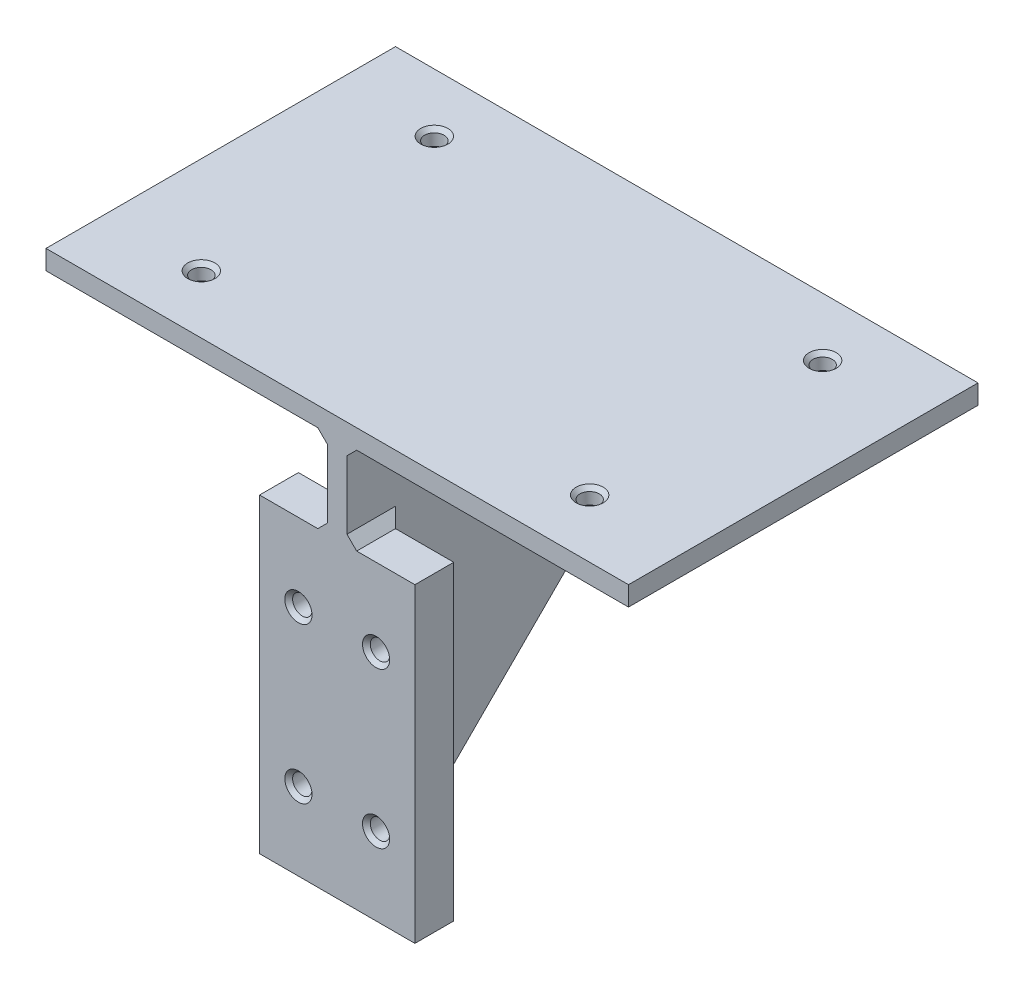
SolidWorks part; units mm, degrees
ref_plane "Front Plane" through (0, 0, 0) normal (0, 0, 1) x (1, 0, 0)
ref_plane "Top Plane" through (0, 0, 0) normal (0, 1, 0) x (1, 0, 0)
ref_plane "Right Plane" through (0, 0, 0) normal (1, 0, 0) x (0, 0, -1)
sketch "Sketch1" plane through (0, 0, 0) normal (0, 0, 1) x (1, 0, 0)
  line L1 (-20, -40) -> (20, -40)
  line L2 (-20, -40) -> (-20, 40)
  line L3 (-20, 40) -> (20, 40)
  line L4 (20, -40) -> (20, 40)
  line L5 (-20, -40) -> (20, 40) construction
  line L6 (-20, 40) -> (20, -40) construction
  point P0 (0, 0)
  dimension "D1" = 40
  dimension "D2" = 80
extrude "Boss-Extrude1" add sketch "Sketch1" along normal blind 10
sketch "Sketch2" plane through (0, 0, 10) normal (0, 0, 1) x (1, 0, 0)
  line L0 (0, 20) -> (0, -20) construction
  line L1 (-10, -20) -> (10, -20) construction
  line L2 (-10, -20) -> (-10, 20) construction
  line L3 (-10, 20) -> (10, 20) construction
  line L4 (10, -20) -> (10, 20) construction
  line L5 (-10, -20) -> (10, 20) construction
  line L6 (-10, 20) -> (10, -20) construction
  line L7 (-10, 0) -> (10, 0) construction
  circle A0 centre (-10, -20) radius 2.5
  circle A1 centre (10, -20) radius 2.5
  circle A2 centre (10, 20) radius 2.5
  circle A3 centre (-10, 20) radius 2.5
  point P0 (0, 0)
  dimension "D1" = 5
  dimension "D2" = 40
  dimension "D3" = 20
extrude "Cut-Extrude1" cut sketch "Sketch2" against normal blind 10
sketch "Sketch3" plane through (0, 0, 0) normal (1, 0, 0) x (0, 0, -1)
  line L0 (0, -40) -> (80, 40)
  line L3 (0, -40) -> (0, 40) construction
  line L4 (0, 40) -> (0, -40)
  line L5 (80, 40) -> (80, 65)
  line L8 (0, 40) -> (-10, 40)
  line L9 (-10, 40) -> (-10, 65)
  line L11 (-10, 65) -> (80, 65)
  dimension "D1" = 45
  dimension "D2" = 90
  dimension "D3" = 25
extrude "Boss-Extrude2" add sketch "Sketch3" along normal mid plane 5
sketch "Sketch4" plane through (0, 65, 0) normal (0, 1, 0) x (1, 0, 0)
  line L0 (2.5, 80) -> (-2.5, 80) construction
  line L1 (-75, -10) -> (75, -10)
  line L2 (-75, -10) -> (-75, 80)
  line L3 (-75, 80) -> (75, 80)
  line L4 (75, -10) -> (75, 80)
  line L5 (-75, -10) -> (75, 80) construction
  line L6 (-75, 80) -> (75, -10) construction
  line L7 (20, -10) -> (2.5, -10) construction
  line L8 (0, 0) -> (0, 80) construction
  point P0 (0, 35)
  point P12 (0, 0)
  dimension "D1" = 150
extrude "Boss-Extrude3" add sketch "Sketch4" along normal mid plane 5
chamfer "Chamfer1" distance 2.5 angle 45 6 edges at (-2.5, 40, 5) (-2.5, 0, 0) (2.5, 40, 5) (2.5, 0, 0) (2.5, 62.5, -35) (-2.5, 62.5, -35)
sketch "Sketch5" plane through (0, 67.5, 0) normal (0, 1, 0) x (1, 0, 0)
  line L0 (-75, -10) -> (75, 80) construction
  line L1 (0, 5) -> (0, 65) construction
  line L2 (-50, 5) -> (50, 5) construction
  line L3 (-50, 5) -> (-50, 65) construction
  line L4 (-50, 65) -> (50, 65) construction
  line L5 (50, 5) -> (50, 65) construction
  line L6 (-50, 5) -> (50, 65) construction
  line L7 (-50, 65) -> (50, 5) construction
  line L8 (0, 65) -> (-50, 35) construction
  line L9 (-50, 35) -> (50, 35) construction
  circle A0 centre (50, 65) radius 2.5
  circle A1 centre (50, 5) radius 2.5
  circle A2 centre (-50, 5) radius 2.5
  circle A3 centre (-50, 65) radius 2.5
  point P4 (0, 35)
  dimension "D2" = 5
  dimension "D1" = 100
extrude "Cut-Extrude2" cut sketch "Sketch5" against normal mid plane 70
chamfer "Chamfer2" distance 1 angle 45 16 edges at (-50, 67.5, -67.5) (-50, 62.5, -67.5) (-50, 67.5, -7.5) (-50, 62.5, -7.5) (50, 67.5, -67.5) (50, 62.5, -67.5) (50, 67.5, -7.5) (50, 62.5, -7.5) (-7.5, -20, 10) (-7.5, -20, 0) (7.5, -20, 10) (7.5, -20, 0) (12.5, 20, 10) (12.5, 20, 0) (-12.5, 20, 10) (-12.5, 20, 0)
